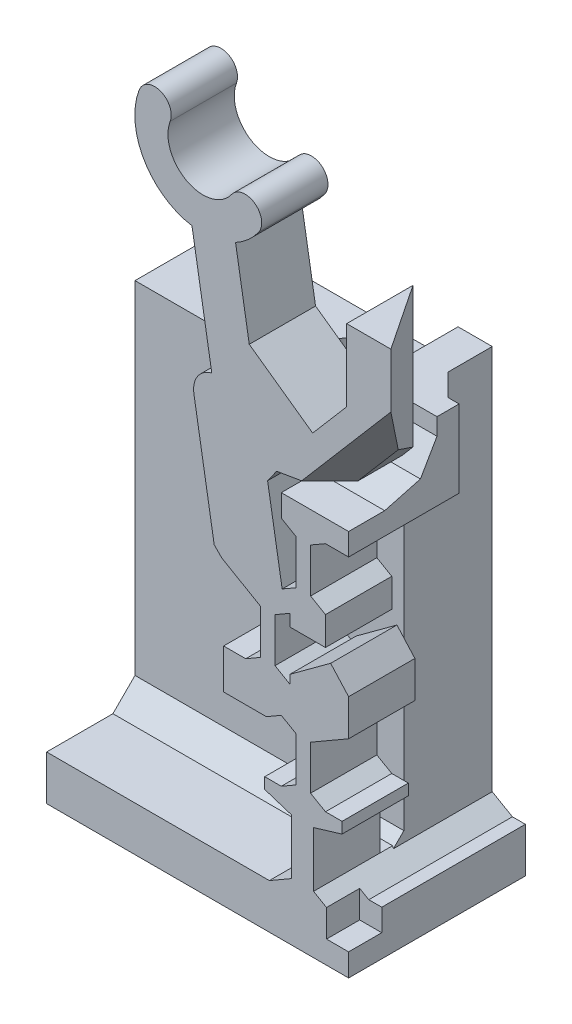
SolidWorks part; units mm, degrees
ref_plane "Front Plane" through (0, 0, 0) normal (0, 0, 1) x (1, 0, 0)
ref_plane "Top Plane" through (0, 0, 0) normal (0, 1, 0) x (1, 0, 0)
ref_plane "Right Plane" through (0, 0, 0) normal (1, 0, 0) x (0, 0, -1)
sketch "Sketch-SkeletonConfigUp" plane through (0, 0, 0) normal (0, 0, 1) x (1, 0, 0)
  line L0 (0, 0) -> (0, -50000) construction
  line L1 (0, 0) -> (4.5811, 6.2164) construction
  line L2 (9.8143, 13.3177) -> (4.5811, 13.945) construction
  line L3 (4.5811, 13.945) -> (2.9713, 10.4094) construction
  line L4 (2.9713, 10.4094) -> (4.5811, 6.2164) construction
  line L5 (4.5811, 13.945) -> (6.2429, 19.1409) construction
  line L6 (2.9713, 10.4094) -> (0.0405, 27.8193) construction
  line L7 (4.5811, 6.2164) -> (9.8143, 13.3177) construction
  line L8 (-587.3593, -797.0242) -> (9.8143, 13.3177) construction
  dimension "D2" = 7.7221
  dimension "D3" = 8.8212
  dimension "D4" = 5.2707
  dimension "D5" = 119.553
  dimension "D6" = 3.8848
  dimension "D7" = 5.4552
  dimension "D8" = 17.6549
  dimension "D9" = 4.4914
  dimension "D10" = 6.745
  dimension "D11" = 145.964
  dimension "D12" = 143.612
sketch "Sketch-SkeletonConfigDown" plane through (0, 0, 0) normal (0, 0, 1) x (1, 0, 0)
  line L0 (0, 0) -> (0, -50000) construction
  line L1 (0, 0) -> (4.5811, 6.2164) construction
  line L2 (9.8143, 13.3177) -> (4.5811, 13.945) construction
  line L3 (4.5811, 13.945) -> (6.1909, 10.4094) construction
  line L4 (6.1909, 10.4094) -> (4.5811, 6.2164) construction
  line L5 (4.5811, 13.945) -> (1.753, 18.6098) construction
  line L6 (6.1909, 10.4094) -> (-8.8652, 19.6294) construction
  line L7 (4.5811, 6.2164) -> (9.8143, 13.3177) construction
  line L8 (-589.9357, -800.5203) -> (9.8143, 13.3177) construction
  dimension "D2" = 7.7221
  dimension "D3" = 8.8212
  dimension "D4" = 5.2707
  dimension "D5" = 119.553
  dimension "D6" = 3.8848
  dimension "D7" = 5.4552
  dimension "D8" = 17.6549
  dimension "D9" = 4.4914
  dimension "D10" = 6.745
  dimension "D11" = 145.964
  dimension "D1" = 143.612
ref_plane "Plane-Cam Base" through (9.128, 0, 0) normal (1, 0, 0) x (0, 0, -1)
ref_plane "Plane-Down-to-Up Derailleur Clearance" through (6.628, 0, 0) normal (1, 0, 0) x (0, 0, -1)
ref_plane "Plane-Cam Cavity Roof" through (5.128, 0, 0) normal (1, 0, 0) x (0, 0, -1)
sketch "Sketch-SwitchBossUp" plane through (0, 0, 0) normal (0, 0, 1) x (1, 0, 0)
  line L0 (3.5811, 11.4759) -> (3.5811, 12.945) construction
  line L2 (6.5405, 21.1774) -> (6.5405, 24.4384)
  line L3 (6.5405, 24.4384) -> (8.5405, 24.4384)
  line L4 (8.5405, 24.4384) -> (8.5405, 20.4384)
  line L5 (5.5811, 12.5552) -> (5.5811, 11.263)
  line L7 (1.5115, 25.1048) -> (2.5464, 18.9575)
  line L8 (-0.4607, 24.7728) -> (0.4359, 19.4465)
  line L9 (2.9713, 10.4094) -> (0.0405, 27.8193) construction
  line L11 (-0.0396, 22.2712) -> (1.9326, 22.6032) construction
  line L15 (6.628, -23.7286) -> (6.628, 23.7286) construction
  line L16 (2.9713, 10.4094) -> (4.5811, 6.2164) construction
  line L17 (3.5811, 12.945) -> (3.5811, 14.945) construction
  line L18 (5.5811, 12.945) -> (5.5811, 14.945) construction
  line L19 (4.2561, 13.945) -> (4.9061, 13.945) construction
  line L20 (3.5811, 14.945) -> (5.5811, 14.945) construction
  line L21 (3.5811, 12.945) -> (5.5811, 12.945) construction
  line L22 (4.5811, 12.945) -> (4.5811, 14.945) construction
  line L23 (4.5811, 6.2164) -> (8.5405, 7.1023) construction
  line L24 (1.9713, 9.4094) -> (1.9713, 11.4094) construction
  line L25 (3.9713, 9.4094) -> (3.9713, 11.4094) construction
  line L26 (3.9713, 9.4094) -> (1.9713, 9.4094) construction
  line L27 (1.9713, 11.4094) -> (3.9713, 11.4094) construction
  line L28 (3.5811, 7.2164) -> (5.5811, 7.2164) construction
  line L29 (3.5811, 7.2164) -> (3.5811, 5.2164) construction
  line L30 (5.5811, 7.2164) -> (5.5811, 5.2164) construction
  line L31 (3.5811, 5.2164) -> (5.5811, 5.2164) construction
  line L32 (4.9061, 6.2164) -> (4.2561, 6.2164) construction
  line L40 (3.2963, 10.4094) -> (2.6463, 10.4094) construction
  line L43 (2.874, 4.5093) -> (0.7934, 4.5093) construction
  line L46 (5.0405, 1.437) -> (5.0405, 3.937)
  line L51 (4.9929, 19.3693) -> (2.5464, 18.9575)
  line L66 (0.0405, 27.8193) -> (0.0405, 50027.8193) construction
  line L74 (0.5455, 12.7717) -> (-0.3728, 18.2264)
  line L75 (0.3841, 13.7302) -> (2.3564, 14.0622) construction
  line L76 (5.5811, 11.263) -> (5.5811, 12.5552) construction
  line L77 (5.5811, 7.6061) -> (6.628, 8.2105)
  line L80 (5.8152, 10.763) -> (6.628, 9.8603)
  line L81 (8.5405, 1033.6218) -> (8.5405, 20.4384) construction
  line L82 (2.5464, 18.9575) -> (3.5585, 12.945) construction
  line L83 (3.6203, 12.5779) -> (2.8784, 16.9852)
  line L84 (2.8784, 16.9852) -> (6.0405, 17.5175)
  line L85 (6.9307, 9.5241) -> (8.5405, 7.7363) construction
  line L88 (3.5811, 16.3347) -> (6.8573, 16.3347)
  line L92 (3.7762, 8.3129) -> (6.9307, 9.5241) construction
  line L93 (6.3311, 4.3267) -> (5.0405, 3.937)
  line L95 (2.5464, 18.9575) -> (2.8784, 16.9852) construction
  line L96 (2.7124, 17.9713) -> (8.5405, 18.9524) construction
  line L97 (2.7124, 17.9713) -> (1.7262, 17.8053) construction
  line L98 (1.9713, 9.0197) -> (0.9713, 9.0197)
  line L99 (0.9713, 9.0197) -> (0.9713, 7.2164)
  line L100 (0.9713, 7.2164) -> (2.9061, 7.2164)
  line L101 (4.5811, 6.2164) -> (6.9307, 9.5241) construction
  line L103 (0.0405, 27.8193) -> (1.9448, 26.4638) construction
  line L104 (6.9307, 9.5241) -> (8.5405, 7.7363) construction
  line L106 (13.4416, 14.945) -> (5.5811, 14.945) construction
  line L107 (1.9713, 9.4094) -> (1.9713, 9.0197) construction
  line L109 (0.0405, 27.8193) -> (-2.1498, 28.6358) construction
  line L110 (8.5405, 20.4384) -> (6.0405, 17.5175)
  line L111 (6.628, 9.8603) -> (6.628, 8.2105)
  line L112 (6.628, 9.8603) -> (6.9307, 9.5241) construction
  line L113 (2.8311, 4.8267) -> (2.8311, 4.3267)
  line L114 (7.3693, 7.7363) -> (7.3563, 7.7363) construction
  line L115 (6.8573, 16.3347) -> (13.4416, 16.3347)
  line L116 (13.4416, 16.3347) -> (13.4416, -1.1653)
  line L117 (13.4416, -1.1653) -> (5.0405, -1.1653)
  line L119 (10.4375, 14.0252) -> (10.4375, 2.1692)
  line L121 (5.0405, -1.1653) -> (5.0405, 1.437) construction
  line L122 (8.237, 12.8031) -> (10.8393, 12.8031) construction
  line L123 (10.8393, 12.8031) -> (13.4416, 12.8031) construction
  line L124 (10.4375, 2.1692) -> (9.128, 0.8597)
  line L125 (8.5405, 7.5847) -> (13.4416, 7.5847) construction
  line L127 (5.5811, 15.3347) -> (5.5811, 14.945) construction
  line L130 (6.0405, 0.8597) -> (9.128, 0.8597)
  line L132 (2.8311, 4.3267) -> (4.0405, 3.937)
  line L133 (2.9713, 10.4094) -> (6.1909, 10.4094) construction
  line L134 (4.5811, 10.4094) -> (4.5811, 13.945) construction
  line L135 (4.5811, 10.4094) -> (4.5811, 6.2164) construction
  line L136 (0.8973, 12.4192) -> (0.5455, 12.7717)
  line L137 (3.9713, 9.4094) -> (5.5811, 7.2164) construction
  line L139 (5.8152, 10.763) -> (3.9713, 9.4094)
  line L140 (4.0405, 3.937) -> (4.0405, 1.437)
  line L141 (4.0405, 1.437) -> (3.0405, 0.8597)
  line L142 (3.0405, 0.8597) -> (3.0405, -1.1653)
  line L143 (8.5405, 20.4384) -> (8.5405, 18.9524) construction
  line L145 (8.5405, 17.9384) -> (8.5405, -49992.0368) construction
  line L147 (5.5811, 11.263) -> (5.5811, 12.5552) construction
  line L149 (6.3311, 4.8267) -> (6.3311, 4.3267)
  line L150 (3.0405, -1.1653) -> (5.0405, -1.1653)
  line L151 (4.0405, 3.937) -> (5.0405, 3.937) construction
  line L152 (4.2561, 14.945) -> (4.2561, 12.945)
  line L153 (4.9061, 14.945) -> (4.9061, 12.945)
  line L155 (4.2561, 14.945) -> (3.5811, 15.3347)
  line L156 (4.9061, 14.945) -> (5.5811, 15.3347)
  line L157 (3.5811, 16.3347) -> (3.5811, 15.3347)
  line L158 (5.5811, 15.3347) -> (9.128, 15.3347)
  line L162 (3.2963, 11.4094) -> (3.2963, 9.4094)
  line L164 (2.6463, 11.4094) -> (2.6463, 9.4094)
  line L169 (4.2561, 7.2164) -> (4.2561, 5.2164)
  line L170 (4.9061, 5.2164) -> (4.9061, 7.2164)
  line L175 (4.2561, 7.2164) -> (3.5811, 7.6061)
  line L176 (4.9061, 7.2164) -> (5.5811, 7.6061)
  line L177 (5.5811, 7.2164) -> (5.5811, 7.6061) construction
  line L179 (4.2561, 5.2164) -> (3.5811, 4.8267)
  line L180 (3.5811, 5.2164) -> (3.5811, 4.8267) construction
  line L181 (3.5811, 4.8267) -> (2.8311, 4.8267)
  line L183 (4.9061, 5.2164) -> (5.5811, 4.8267)
  line L184 (5.5811, 5.2164) -> (5.5811, 4.8267) construction
  line L186 (9.128, -23.7286) -> (9.128, 23.7286) construction
  line L187 (2.6463, 9.4094) -> (1.9713, 9.0197)
  line L188 (3.2963, 9.4094) -> (3.9713, 9.0197)
  line L189 (3.2963, 11.4094) -> (3.9713, 11.7991)
  line L190 (2.6463, 11.4094) -> (0.8973, 12.4192)
  line L191 (3.9713, 11.4094) -> (3.9713, 11.7991) construction
  line L192 (3.9713, 11.7991) -> (3.9713, 11.263)
  line L193 (4.9061, 12.945) -> (5.5811, 12.5552)
  line L194 (4.2561, 12.945) -> (3.6203, 12.5779)
  line L195 (3.9713, 11.263) -> (5.5811, 11.263)
  line L196 (3.9713, 9.4094) -> (3.9713, 9.0197)
  line L197 (3.5811, 7.2164) -> (3.5811, 7.6061) construction
  line L199 (3.5811, 7.6061) -> (2.9061, 7.2164)
  line L200 (5.5811, 4.8267) -> (6.3311, 4.8267)
  line L201 (2.8311, 4.3267) -> (2.8311, 3.937) construction
  line L202 (2.8311, 3.937) -> (4.0405, 3.937) construction
  line L203 (10.4375, 14.0252) -> (9.128, 15.3347)
  line L204 (4.0405, 1.437) -> (3.0405, 1.437) construction
  line L205 (3.0405, 1.437) -> (3.0405, 0.8597) construction
  line L206 (5.0405, 1.437) -> (6.0405, 0.8597)
  line L207 (8.5405, 18.9524) -> (8.5405, 17.9384) construction
  line L208 (6.0405, 17.5175) -> (8.5405, 17.9384) construction
  line L209 (8.5405, 20.4384) -> (8.5405, 17.9384) construction
  line L210 (6.5405, 21.1774) -> (4.9929, 19.3693)
  arc A0 (1.5115, 25.1048) -> (2.5558, 26.0289) centre (0.0405, 27.8193) ccw
  arc A1 (-0.4607, 24.7728) -> (-2.8525, 28.8978) centre (0.0405, 27.8193) cw
  arc A2 (-2.8525, 28.8978) -> (-1.447, 28.3738) centre (-2.1498, 28.6358) cw
  arc A3 (2.5558, 26.0289) -> (1.3338, 26.8987) centre (1.9448, 26.4638) ccw
  arc A4 (-1.447, 28.3738) -> (1.3338, 26.8987) centre (0.0405, 27.8193) ccw
  arc A5 (3.5811, 12.945) -> (3.5811, 14.945) centre (3.1778, 13.945) ccw construction
  arc A6 (5.5811, 12.945) -> (5.5811, 14.945) centre (5.9843, 13.945) cw construction
  arc A7 (2.5293, 9.921) -> (1.9713, 11.4094) centre (1.568, 10.4094) ccw construction
  arc A8 (3.9713, 11.4094) -> (3.9713, 9.4094) centre (4.3745, 10.4094) ccw construction
  arc A9 (3.5811, 7.2164) -> (3.5811, 5.2164) centre (3.1779, 6.2164) cw construction
  arc A10 (5.5811, 7.2164) -> (5.5811, 5.2164) centre (5.9844, 6.2164) ccw construction
  arc A19 (-0.3728, 18.2264) -> (0.4359, 19.4465) centre (0.6836, 18.4042) cw
  circle A28 centre (0.0405, 27.8193) radius 2.3375 construction
  arc A29 (1.9713, 9.4094) -> (2.5293, 9.921) centre (1.568, 10.4094) ccw construction
  point P53 (4.5811, 13.945)
  point P63 (2.9713, 10.4094)
  point P93 (0.9465, 22.4372)
  dimension "D23" = 1.5875
  dimension "D24" = 0.75
  dimension "D2" = 2
  dimension "D5" = 2
  dimension "D6" = 0.65
  dimension "D8" = 42
  dimension "D7" = 2
  dimension "D10" = 5
  dimension "D11" = 8.5
  dimension "D14" = 7.5
  dimension "D4" = 3
  dimension "D16" = 42
  dimension "D12" = 1
  dimension "D13" = 2.5
  dimension "D25" = 120
  dimension "D26" = 120
  dimension "D27" = 120
  dimension "D28" = 120
  dimension "D29" = 120
  dimension "D30" = 120
  dimension "D31" = 120
  dimension "D32" = 120
  dimension "D33" = 120
  dimension "D34" = 120
  dimension "D35" = 120
  dimension "D36" = 120
  dimension "D17" = 0.5
  dimension "D20" = 3.5
  dimension "D21" = 1
  dimension "D18" = 45
  dimension "D9" = 17.5
  dimension "D22" = 1
  dimension "D19" = 120
  dimension "D37" = 120
  dimension "D15" = 45
  dimension "D38" = 2
  dimension "D39" = 0.5
  dimension "D40" = 60
  dimension "D41" = 1
  dimension "D42" = 45
  dimension "D43" = 120
  dimension "D44" = 2
  dimension "D45" = 2.5
  dimension "D46" = 2.5
  dimension "D47" = 4
  dimension "D48" = 2
extrude "Boss-Switch Main" add sketch "Sketch-SwitchBossUp" along normal blind 3
sketch "Sketch1" plane through (0, 0, 0) normal (0, 0, -1) x (-1, 0, 0)
  line L0 (-3.5811, 16.3347) -> (-3.5811, 15.3347) construction
  line L1 (-7.5811, -1.1653) -> (0.4122, -1.1653)
  line L2 (-7.5811, -1.1653) -> (-7.5811, 0.8597)
  line L4 (0.4122, -1.1653) -> (0.4122, 0.8597)
  line L5 (-3.5811, 18.8347) -> (-7.5811, 18.8347)
  line L10 (-7.5811, 18.8347) -> (-7.5811, 15.3347)
  line L11 (-4.0405, 1.437) -> (-5.0405, 1.437)
  line L12 (-7.5811, 15.3347) -> (-3.5811, 15.3347)
  line L13 (-4.0405, 1.437) -> (-3.0405, 0.8597)
  line L14 (-3.5811, 15.3347) -> (-3.5811, 18.8347)
  line L22 (-3.0405, -1.1653) -> (-13.4416, -1.1653) construction
  line L23 (-3.0405, 0.8597) -> (0.4122, 0.8597)
  line L24 (-5.0405, 1.437) -> (-6.0405, 0.8597)
  line L25 (-6.0405, 0.8597) -> (-7.5811, 0.8597)
  line L26 (-9.128, 15.3347) -> (-5.5811, 15.3347) construction
  dimension "D1" = 3.5
  dimension "D4" = 4
extrude "Boss-Flange Width" add sketch "Sketch1" along normal blind 5
ref_plane "Plane-Sta2Sit Groove" through (0.0405, 0, 0) normal (1, 0, 0) x (0, 0, -1)
ref_plane "Plane-Cam Outer Surface" through (-12.0395, 0, 0) normal (1, 0, 0) x (0, 0, -1)
ref_plane "Plane-FlangeTop" through (-7.0395, 0, 0) normal (1, 0, 0) x (0, 0, -1)
sketch "Sketch2" plane through (-7.0395, 0, 0) normal (1, 0, 0) x (0, 0, -1)
  line L0 (5, 15.3347) -> (0, 15.3347) construction
  line L1 (5, 17.3347) -> (1, 17.3347)
  line L2 (5, 17.3347) -> (5, 15.3347)
  line L3 (5, 15.3347) -> (1, 15.3347)
  line L4 (1, 17.3347) -> (1, 15.3347)
  line L10 (-3, -1.1653) -> (-3, 16.3347) construction
  line L11 (5, 0.8597) -> (-3, 0.8597)
  line L12 (5, 0.8597) -> (5, -1.1653)
  line L13 (5, -1.1653) -> (-3, -1.1653)
  line L14 (-3, 0.8597) -> (-3, -1.1653)
  line L15 (0, 10.4094) -> (0, 27.8193) construction
  line L17 (5, 0.8597) -> (5, -1.1653) construction
  line L18 (-3, 0.8597) -> (0, 0.8597) construction
  dimension "D1" = 1
  dimension "D2" = 2
extrude "Boss-Flange Height" add sketch "Sketch2" along normal up to surface (11.6675 mm away)
sketch "Sketch10" plane through (0, 15.3347, 0) normal (0, 1, 0) x (1, 0, 0)
  line L0 (9.128, -23.7286) -> (9.128, 23.7286) construction
  line L1 (7.5811, 5) -> (5.128, 5)
  line L2 (7.5811, 5) -> (7.5811, 2)
  line L3 (7.5811, 2) -> (5.128, 2)
  line L5 (4.628, 7) -> (4.628, 1) construction
  line L6 (3.5811, 1) -> (-7.0395, 1) construction
  line L8 (5.128, 5) -> (5.128, 2)
  point P1 (0, 0)
  point P4 (7.5811, 5)
  dimension "D1" = 1
  dimension "D2" = 0.5
  dimension "D3" = 4.5
extrude "Cut-Up-To-Down Derailleur Clearance" cut sketch "Sketch10" along normal up to next
sketch "Sketch17" plane through (0, 15.3347, 0) normal (0, -1, 0) x (1, 0, 0)
  line L0 (5.128, -5) -> (-7.0395, -5)
  line L1 (5.128, -5) -> (3.5811, -5) construction
  line L2 (-7.0395, -5) -> (-7.0395, -1)
  line L3 (-7.0395, -1) -> (5.128, -1)
  line L4 (5.128, -1) -> (5.128, -5)
  line L5 (-7.0395, -1) -> (-7.0395, -5) construction
extrude "Boss-Flange Support" add sketch "Sketch17" along normal up to surface (14.475 mm away) up to face at (-1.9995, 0.8597, -1)
sketch "Sketch-HolePositions" plane through (0, -1.1653, 0) normal (0, -1, 0) x (1, 0, 0)
  line L0 (-7.0395, -3) -> (7.5811, -3) construction
  line L1 (7.5811, -5) -> (-7.0395, -5) construction
  line L2 (7.5811, -5) -> (7.5811, 0) construction
  line L4 (-7.0395, -22.2167) -> (-7.0395, 22.2167) construction
  line L5 (3.5811, -1) -> (3.5811, -5) construction
  point P6 (-4.0395, -3)
  point P7 (0.5811, -3)
  dimension "D1" = 3
  dimension "D2" = 3
  dimension "D3" = 2
sketch "Sketch6" plane through (0, -1.1653, 0) normal (0, -1, 0) x (-1, 0, 0)
  point P0 (4.0395, 3)
  point P3 (-0.5811, 3)
hole_wizard "Tap Drill for M2x0.4 Tap1" positions "Sketch6" profile "Sketch5" hole size "M2x0.4" standard "ANSI Metric" end condition through all
sketch "Sketch5" plane through (-4.0395, -1.1653, -3) normal (1, 0, 0) x (0, 0, -1)
  line L0 (0, 0) -> (0, 30.5511)
  line L1 (0, 30.5511) -> (0.8, 30.5511)
  line L2 (0.8, 30.5511) -> (0.8, 0)
  line L5 (0.8, 0) -> (0, 0)
  line L11 (0, -6.35) -> (0, 107.95) construction
  dimension "Thru Hole Dia." = 1.6
  dimension "Thru Hole Depth" = 30.5511
sketch "Sketch9" plane through (0, -1.1653, 0) normal (0, -1, 0) x (1, 0, 0)
  point P0 (-4.0395, -3)
  point P3 (0.5811, -3)
hole_wizard "M2 Clearance Hole2" positions "Sketch9" profile "Sketch8" hole size "M2" standard "ANSI Metric"
sketch "Sketch8" plane through (-4.0395, -1.1653, -3) normal (1, 0, 0) x (0, 0, -1)
  line L0 (0, 0) -> (0, 15.721)
  line L1 (0, 15.721) -> (1.2, 15)
  line L2 (1.2, 15) -> (1.2, 0)
  line L5 (1.2, 0) -> (0, 0)
  line L10 (0, 15.721) -> (-1.2, 15) construction
  line L11 (0, -6.35) -> (0, 107.95) construction
  dimension "Hole Dia." = 2.4
  dimension "Hole Depth" = 15
  dimension "Drill Angle" = 118
sketch "Sketch-Measurements for Derailleur Ramps" plane through (0, 0, 0) normal (0, 0, 1) x (1, 0, 0)
  line L0 (2.8784, 16.9852) -> (2.5464, 18.9575)
  line L1 (2.7124, 17.9713) -> (1.7262, 17.8053)
  line L2 (2.9713, 10.4094) -> (0.0405, 27.8193) construction
  line L3 (1.7262, 17.8053) -> (-1.8937, 15.3603)
  line L4 (6.1909, 10.4094) -> (-8.8652, 19.6294) construction
  line L5 (1.7262, 17.8053) -> (2.6012, 12.6077)
  line L6 (2.6012, 12.6077) -> (-1.8937, 15.3603)
  line L7 (-0.0837, 16.5828) -> (-0.0837, 17.8053)
  line L8 (-0.0837, 17.8053) -> (1.7262, 17.8053)
  line L9 (6.1909, 10.4094) -> (2.9713, 10.4094)
  line L10 (5.386, 8.3129) -> (3.7762, 8.3129)
  line L12 (6.1909, 10.4094) -> (4.5811, 6.2164) construction
  line L13 (4.5811, 8.3129) -> (4.5811, 8.7912)
  line L14 (4.5811, 6.2164) -> (5.386, 8.3129)
  line L15 (2.9713, 10.4094) -> (4.5811, 6.2164) construction
  line L16 (3.7762, 8.3129) -> (4.5811, 6.2164)
  line L17 (5.386, 8.3129) -> (5.386, 8.7912)
  dimension "D1" = 1.81
  dimension "D2" = 0.8049
sketch "Sketch12" plane through (0, 24.4384, 0) normal (0, 1, 0) x (1, 0, 0)
  line L0 (6.5405, 0) -> (8.5405, -3)
  line L1 (8.5405, -3) -> (8.5405, 0)
  line L2 (8.5405, 0) -> (6.5405, 0)
extrude "Cut-Up-to-Down Cantilever Slope" cut sketch "Sketch12" against normal up to next
ref_plane "Plane1" through (0, 7.1023, 0) normal (0, 1, 0) x (1, 0, 0)
sketch "Sketch-Derailleur Location" plane through (0, 7.1023, 0) normal (0, 1, 0) x (1, 0, 0)
  line L0 (8.5405, 0) -> (8.5405, -3)
  line L1 (4.0405, -3) -> (3.0405, -3) construction
  line L2 (-119237.4187, 0) -> (9.8143, 0) construction
  point P0 (8.5405, 0)
  point P8 (8.5405, -1.5)
ref_plane "Plane-Cantilever Cut" [suppressed] through (7.0848, 8.5204, -1.9058) normal (-0.6301, -0.7578, 0.1695) x (-0.7765, 0.6151, -0.1368)
sketch "Sketch14" [suppressed] plane through (7.0848, 8.5204, -1.9058) normal (-0.6301, -0.7578, 0.1695) x (-0.7765, 0.6151, -0.1368)
  line L0 (2.3023, -1.6911) -> (-0.3551, -1.6911)
  line L2 (2.3023, -4.3362) -> (2.3023, -1.6911)
  line L3 (-0.3551, -1.6911) -> (-0.3551, -4.4608)
  line L5 (-0.3551, -4.4608) -> (1.0087, -5.0843)
  line L6 (1.0087, -5.0843) -> (2.3023, -4.3362)
extrude "Cut-Down-to-Up Cantilever Slope" [suppressed] cut sketch "Sketch14" against normal up to next
sketch "Sketch16" plane through (0, 0, 0) normal (0, 0, -1) x (-1, 0, 0)
  line L0 (-7.5811, 18.8347) -> (-13.4416, 18.8347)
  line L1 (-13.4416, 18.8347) -> (-13.4416, -1.1653)
  line L2 (-13.4416, -1.1653) -> (-6.628, -1.1653)
  line L3 (-13.4416, -1.1653) -> (-5.0405, -1.1653) construction
  line L4 (-6.628, -1.1653) -> (-6.628, 5.2038)
  line L5 (-6.628, 5.2038) -> (-8.0037, 5.2038)
  line L6 (-8.0037, 5.2038) -> (-8.0037, 12.0484)
  line L7 (-8.0037, 12.0484) -> (-6.628, 12.0484)
  line L8 (-6.628, 12.0484) -> (-6.628, 17.9477)
  line L9 (-6.628, 23.7286) -> (-6.628, -23.7286) construction
  line L10 (-3.5811, 18.8347) -> (-6.5405, 18.8347) construction
  line L11 (-7.5811, 18.8347) -> (-6.628, 17.9477)
  point P0 (-7.5811, 18.8347)
extrude "Cut-Down-to-Up Derailleur Clearance" cut sketch "Sketch16" against normal through all and the other way through all
ref_plane "Plane-Symmetry Plane" through (0, 0, 1.5) normal (0, 0, 1) x (1, 0, 0)
sketch "Sketch-Cable Center Point" plane through (0, 0, 1.5) normal (0, 0, 1) x (1, 0, 0)
  line L0 (0.0405, 27.8193) -> (0.1722, 27.0366)
  line L1 (2.9713, 10.4094) -> (0.0405, 27.8193) construction
  point P0 (0.0405, 27.8193)
  dimension "D1" = 0.7937
chamfer "Chamfer-Flange Support" distance 1.5 angle 45 1 edges at (3.5811, 17.3347, -3)
chamfer "Chamfer-Flange Support 2" distance 1 angle 45 2 edges at (5.128, 17.0847, -2) (5.128, 15.3347, -1.5)
chamfer "Chamfer-Flange Support 3" distance 1 angle 45 1 edges at (-1.9995, 0.8597, -1)
sketch "Sketch18" plane through (6.628, 0, 0) normal (1, 0, 0) x (0, 0, -1)
  line L1 (-3, -0.1403) -> (-1.5, -0.1403)
  line L2 (-3, -0.1403) -> (-3, 1.437)
  line L3 (-3, 1.437) -> (-1.5, 1.437)
  line L4 (-1.5, -0.1403) -> (-1.5, 1.437)
  line L5 (0.5774, 1.437) -> (0, 1.437) construction
  line L6 (-3, -1.1653) -> (-3, 0.8597) construction
  line L7 (-3, 0.8597) -> (5, 0.8597) construction
  dimension "D1" = 1.5
  dimension "D2" = 1
extrude "Cut-Down-to-Up Derailleur Clearance 2" cut sketch "Sketch18" against normal blind 1
sketch "Sketch19" plane through (0, 0, 0) normal (0, 0, 1) x (1, 0, 0)
  line L7 (3.5811, 18.8347) -> (6.628, 18.8347)
  line L8 (6.628, 18.8347) -> (6.628, 16.3347)
  line L9 (6.628, 16.3347) -> (3.5811, 16.3347)
  line L10 (3.5811, 16.3347) -> (3.5811, 18.8347)
  line L11 (6.628, 16.3347) -> (6.628, 17.9477) construction
  point P5 (0, 0)
  point P6 (3.5811, 18.8347)
  point P8 (3.5811, 18.8347)
extrude "Cut-Up-to-Down Cantilever Clearance" cut sketch "Sketch19" against normal up to surface (1 mm away) up to face at (1.4435, 12.7784, -1)
chamfer "Chamfer1" distance 1 angle 60 1 edges at (5.1045, 16.3347, -1) first distance on face at (5.1045, 16.3347, 1)
chamfer "Chamfer3" distance 0.75 angle 60 1 edges at (3.5811, 16.7007, -1) first distance on face at (3.5811, 16.1233, 0.6667)
chamfer "Chamfer4" distance 0.5 angle 60 1 edges at (4.205, 15.3347, -1) first distance on face at (5.1242, 15.3347, -0.0278)
chamfer "Chamfer5" distance 0.5 angle 45 1 edges at (2.8784, 16.9852, 1.5)
chamfer "Chamfer6" distance 2.5 angle 45 1 edges at (2.5464, 18.9575, 1.5)
chamfer "Chamfer7" distance 1 angle 45 1 edges at (7.2905, 18.978, 3)
sketch "Sketch22" plane through (0, 0, 0) normal (0, 0, 1) x (1, 0, 0)
  line L0 (6.628, 17.9477) -> (7.5811, 18.8347) construction
  line L1 (6.628, 18.8347) -> (7.5811, 18.8347) construction
  line L2 (6.628, 17.9477) -> (6.628, 18.8347) construction
  line L3 (6.628, 17.9477) -> (7.5811, 18.8347)
  line L4 (6.628, 18.8347) -> (7.5811, 18.8347)
  line L5 (6.628, 17.9477) -> (6.628, 18.8347)
extrude "Cut-Extrude3" cut sketch "Sketch22" against normal up to next
chamfer "Chamfer8" distance 0.5 angle 45 1 edges at (5.1045, 16.3347, 0) first distance on face at (4.2965, 17.2286, -0.5161)
equation "\"axle-diameter\"=2"
equation "\"switch-thickness\"=12"
equation "\"base-width\"=4.0"
equation "\"axle-bushing-radius\"=3"
equation "\"clearance\"= 0.25"
equation "\"arm-width\"=1.5"
equation "\"min-diameter\"=70"
equation "\"alpha\"=143.6120"
equation "\"gamma\"=119.5526"
equation "\"delta\"=145.9637"
equation "\"epsilon\"=6.7452"
equation "\"l_AB\"=8.8212"
equation "\"l_AC\"=4.4914"
equation "\"l_BD\"=5.2707"
equation "\"l_CD\"=3.8848"
equation "\"l_CE\"=17.6549"
equation "\"l_DF\"=5.4552"
equation "\"l_OA\"=7.7221"
equation "\"D2@Sketch-SkeletonConfigUp\" = \"l_OA\""
equation "\"D3@Sketch-SkeletonConfigUp\" = \"l_AB\""
equation "\"D4@Sketch-SkeletonConfigUp\" = \"l_BD\""
equation "\"D5@Sketch-SkeletonConfigUp\" = \"gamma\""
equation "\"D6@Sketch-SkeletonConfigUp\" = \"l_CD\""
equation "\"D7@Sketch-SkeletonConfigUp\" = \"l_DF\""
equation "\"D8@Sketch-SkeletonConfigUp\" = \"l_CE\""
equation "\"D9@Sketch-SkeletonConfigUp\" = \"l_AC\""
equation "\"D_groove\"=3.175"
equation "\"D7@Sketch-SkeletonConfigDown\" = \"l_DF\""
equation "\"D6@Sketch-SkeletonConfigDown\" = \"l_CD\""
equation "\"D2@Sketch-SkeletonConfigDown\" = \"l_OA\""
equation "\"D3@Sketch-SkeletonConfigDown\" = \"l_AB\""
equation "\"D9@Sketch-SkeletonConfigDown\" = \"l_AC\""
equation "\"D8@Sketch-SkeletonConfigDown\" = \"l_CE\""
equation "\"D5@Sketch-SkeletonConfigDown\" = \"gamma\""
equation "\"D4@Sketch-SkeletonConfigDown\" = \"l_BD\""
equation "\"D1@Sketch-SkeletonConfigDown\" = \"alpha\""
equation "\"hinge_length\"=1.5"
equation "\"hinge_depth\"=0.25"
equation "\"D10@Sketch-SkeletonConfigUp\"=\"epsilon\""
equation "\"D11@Sketch-SkeletonConfigUp\"=\"delta\""
equation "\"D12@Sketch-SkeletonConfigUp\"=\"alpha\""
equation "\"D11@Sketch-SkeletonConfigDown\"=\"delta\""
equation "\"D10@Sketch-SkeletonConfigDown\"=\"epsilon\""
equation "\"EE_dx\"=8.9056"
equation "\"EE_dy\"=8.1898"
equation "\"r_groove\"=\"D_groove\"/2"
equation "\"t_wall\"=25.4/16"
equation "\"width_lower\"=\"D_groove\"+\"t_wall\""
equation "\"cable_to_bottom\"=30.6257"
equation "\"switch_EE-up_base_dy\"=24"
equation "\"switch_EE-down_base_dy\"=16"
equation "\"D_axle\"=25.4/8"
equation "\"D_up_to_down\"=16"
equation "\"D_down_to_up\"=25"
equation "\"t_cam_base\"=7.5"
equation "\"D23@Sketch-SwitchBossUp\"=\"D_groove\"/2"
equation "\"D1@Sketch-Cable Center Point\"=\"D_groove\"/4"
